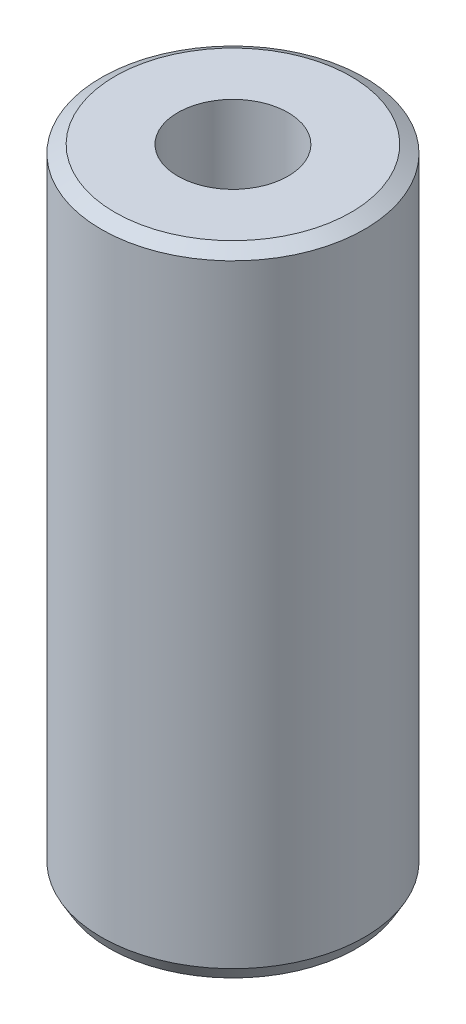
SolidWorks part; units mm, degrees
ref_plane "Front Plane" through (0, 0, 0) normal (0, 0, 1) x (1, 0, 0)
ref_plane "Top Plane" through (0, 0, 0) normal (0, 1, 0) x (1, 0, 0)
ref_plane "Right Plane" through (0, 0, 0) normal (1, 0, 0) x (0, 0, -1)
sketch "Sketch1" plane through (0, 0, 0) normal (0, 1, 0) x (1, 0, 0)
  circle A0 centre (0, 0) radius 50
  dimension "SHAFT_OD" = 100
extrude "Boss-Extrude1" add sketch "Sketch1" along normal blind 241.0841
sketch "Sketch2" plane through (0, 0, 0) normal (0, 1, 0) x (1, 0, 0)
  circle A0 centre (0, 0) radius 20.9532
  dimension "BORE_D" = 41.9065
extrude "Cut-Extrude1" cut sketch "Sketch2" along normal through all
chamfer "Chamfer1" distance 2.9866 angle 60 2 edges at (0, 241.0841, 50) (0, 0, 50) first distance on face at (0, 241.0841, 50) first distance on face at (0, 0, 20.9532)
